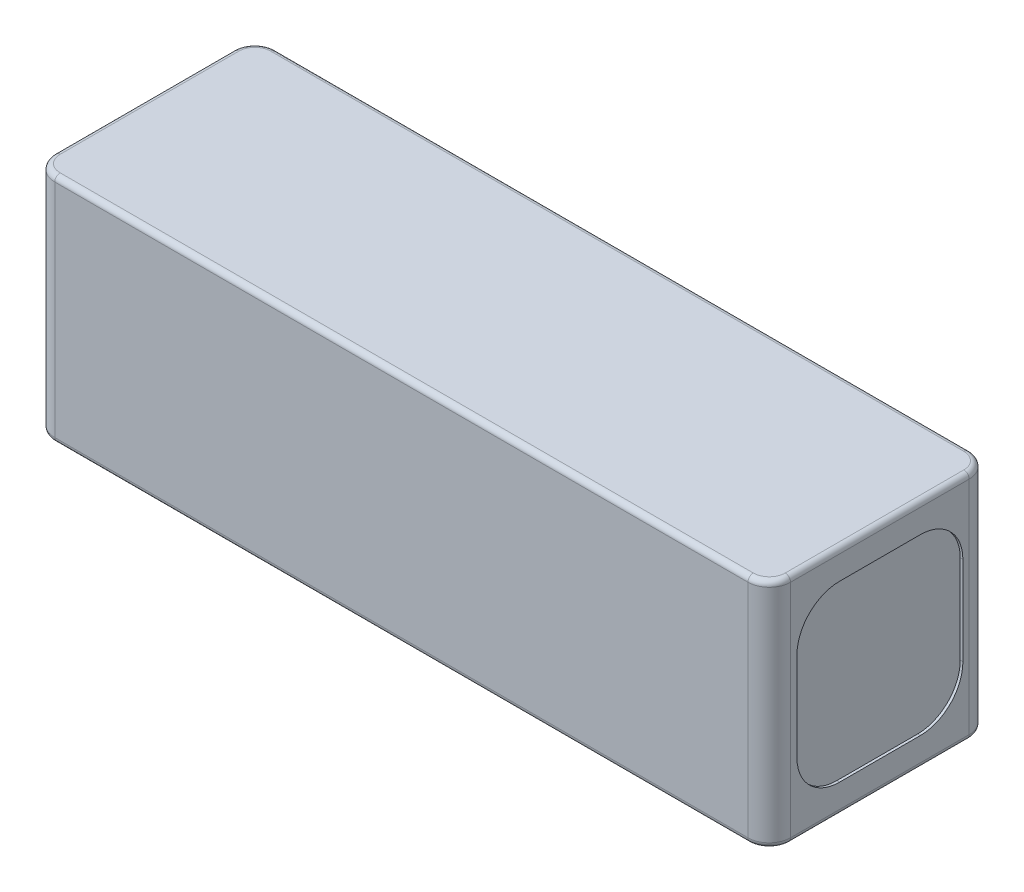
SolidWorks part; units mm, degrees
ref_plane "Front Plane" through (0, 0, 0) normal (0, 0, 1) x (1, 0, 0)
ref_plane "Top Plane" through (0, 0, 0) normal (0, 1, 0) x (1, 0, 0)
ref_plane "Right Plane" through (0, 0, 0) normal (1, 0, 0) x (0, 0, -1)
ref_plane "Plane1" through (0, 0, -15) normal (0, 0, -1) x (-1, 0, 0)
sketch "Sketch1" plane through (0, 0, -15) normal (0, 0, -1) x (-1, 0, 0)
  line L0 (-69, -22) -> (69, -22)
  line L1 (69, -22) -> (69, 21.5)
  line L2 (69, 21.5) -> (-69, 21.5)
  line L3 (-69, 21.5) -> (-69, -22)
  line L4 (-69, -0.25) -> (69, -0.25) construction
  line L5 (0, 21.5) -> (0, -22) construction
  dimension "D1" = 43.5
  dimension "D2" = 138
extrude "Boss-Extrude1" add sketch "Sketch1" against normal blind 41.5
sketch "Sketch2" plane through (69, 0, 0) normal (1, 0, 0) x (0, 0, -1)
  line L0 (-21.3125, 8.0625) -> (-21.3125, -8.5625)
  line L1 (-13.3125, -16.5625) -> (1.8125, -16.5625)
  line L2 (9.8125, -8.5625) -> (9.8125, 8.0625)
  line L3 (1.8125, 16.0625) -> (-13.3125, 16.0625)
  line L4 (-26.5, 21.5) -> (15, -22) construction
  line L5 (15, 21.5) -> (-26.5, -22) construction
  line L6 (-21.3125, 16.0625) -> (9.8125, -16.5625) construction
  line L7 (9.8125, 16.0625) -> (-21.3125, -16.5625) construction
  line L12 (-26.5, 21.5) -> (15, 21.5) construction
  line L13 (-26.5, 21.5) -> (-26.5, -22) construction
  line L14 (-26.5, -22) -> (15, -22) construction
  line L15 (15, 21.5) -> (15, -22) construction
  line L16 (-26.5, 21.5) -> (15, -22) construction
  line L17 (-26.5, -22) -> (15, 21.5) construction
  arc A0 (-21.3125, -8.5625) -> (-13.3125, -16.5625) centre (-13.3125, -8.5625) ccw
  arc A1 (1.8125, -16.5625) -> (9.8125, -8.5625) centre (1.8125, -8.5625) ccw
  arc A2 (9.8125, 8.0625) -> (1.8125, 16.0625) centre (1.8125, 8.0625) ccw
  arc A3 (-21.3125, 8.0625) -> (-13.3125, 16.0625) centre (-13.3125, 8.0625) cw
  point P16 (-5.75, -0.25)
  dimension "D3" = 8
  dimension "D1" = 31.125
  dimension "D2" = 41.5
extrude "Cut-Extrude1" cut sketch "Sketch2" against normal blind 0.5
sketch "Sketch3" plane through (-69, 0, 0) normal (-1, 0, 0) x (0, 0, 1)
  line L0 (13.3125, 16.0625) -> (-1.8125, 16.0625)
  line L1 (-9.8125, 8.0625) -> (-9.8125, -8.5625)
  line L2 (-1.8125, -16.5625) -> (13.3125, -16.5625)
  line L3 (21.3125, -8.5625) -> (21.3125, 8.0625)
  line L4 (-9.8125, 16.0625) -> (21.3125, -16.5625) construction
  line L5 (21.3125, 16.0625) -> (-9.8125, -16.5625) construction
  line L6 (-15, 21.5) -> (26.5, -22) construction
  line L7 (26.5, -22) -> (-15, -22) construction
  line L8 (-15, -22) -> (26.5, 21.5) construction
  arc A0 (-9.8125, -8.5625) -> (-1.8125, -16.5625) centre (-1.8125, -8.5625) ccw
  arc A1 (13.3125, -16.5625) -> (21.3125, -8.5625) centre (13.3125, -8.5625) ccw
  arc A2 (13.3125, 16.0625) -> (21.3125, 8.0625) centre (13.3125, 8.0625) cw
  arc A3 (-1.8125, 16.0625) -> (-9.8125, 8.0625) centre (-1.8125, 8.0625) ccw
  dimension "D3" = 8
  dimension "D1" = 31.125
  dimension "D2" = 41.5
extrude "Cut-Extrude2" cut sketch "Sketch3" against normal blind 0.5
fillet "Fillet1" radius 4 4 edges at (-69, -0.25, -15) (-69, -0.25, 26.5) (69, -0.25, -15) (69, -0.25, 26.5) tangent propagation no
fillet "Fillet2" radius 1 16 edges at (67.8284, 21.5, -13.8284) (69, 21.5, 5.75) (0, 21.5, -15) (67.8284, 21.5, 25.3284) (-67.8284, 21.5, -13.8284) (0, 21.5, 26.5) (-69, 21.5, 5.75) (-67.8284, 21.5, 25.3284) (-69, -22, 5.75) (-67.8284, -22, -13.8284) (-67.8284, -22, 25.3284) (0, -22, -15) (0, -22, 26.5) (67.8284, -22, -13.8284) (67.8284, -22, 25.3284) (69, -22, 5.75) tangent propagation no
sketch "Sketch4" plane through (0, 0, 26.5) normal (0, 0, 1) x (1, 0, 0)
  line L0 (-65, -0.25) -> (65, -0.25) construction
  line L1 (-65, 20.5) -> (-65, -21) construction
  line L2 (65, -21) -> (65, 20.5) construction
  line L3 (0, 25.9735) -> (0, -21) construction
  line L4 (-65, -21) -> (65, -21) construction
  circle A0 centre (0, -0.25) radius 0.5026
equation "\"D1@Sketch3\"=\"D2@Sketch3\" * .75"
equation "\"D1@Sketch2\"=\"D2@Sketch2\"* .75"
